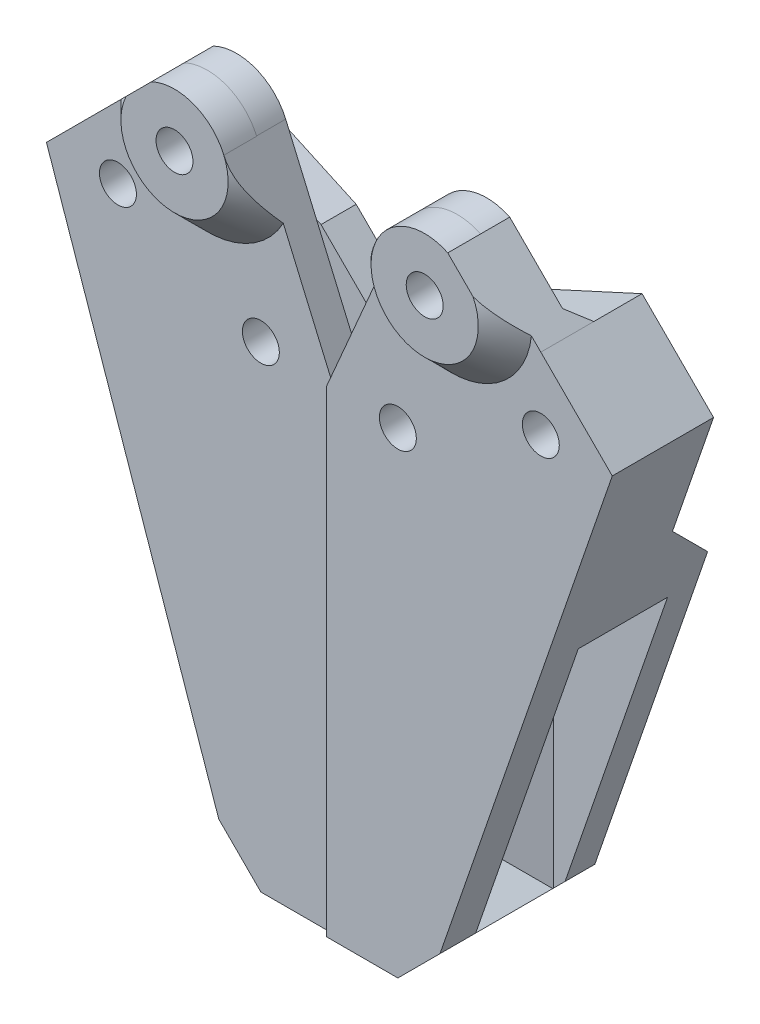
SolidWorks part; units mm, degrees
material "ABS"
ref_plane "Płaszczyzna przednia" through (0, 0, 0) normal (0, 0, 1) x (1, 0, 0)
ref_plane "Płaszczyzna górna" through (0, 0, 0) normal (0, 1, 0) x (1, 0, 0)
ref_plane "Płaszczyzna prawa" through (0, 0, 0) normal (1, 0, 0) x (0, 0, -1)
sketch "Szkic1" plane through (0, 0, 0) normal (0, 0, 1) x (1, 0, 0)
  line L0 (-24, 11) -> (-24, 23)
  line L1 (-24, 11) -> (-36, 11)
  line L2 (-24, 23) -> (-36, 11)
  line L3 (0, 0) -> (0, 12)
  line L4 (0, 12) -> (-24, 23)
  line L5 (0, 0) -> (12, 0)
  line L6 (0, 12) -> (12, 0)
  line L7 (0, 0) -> (0, -80)
  line L8 (0, -80) -> (12, -80)
  line L9 (0, -80) -> (-7.0711, -72.9289)
  line L10 (-7.0711, -72.9289) -> (-36, 11)
  line L11 (12, -80) -> (12, 0)
  circle A0 centre (0, 0) radius 3.1
  circle A1 centre (-24, 11) radius 3.1
  dimension "D1" = 6.2
  dimension "D2" = 24
  dimension "D3" = 6.2
  dimension "D4" = 11
  dimension "D5" = 12
  dimension "D6" = 12
  dimension "D7" = 12
  dimension "D8" = 12
  dimension "D9" = 80
  dimension "D10" = 12
  dimension "D11" = 135
  dimension "D12" = 10
extrude "Dodanie-wyciągnięcie1" add sketch "Szkic1" along normal blind 25 contours A1 L0 L2 L1 | A1 L1 L10 L9 L7 A0 L3 L4 L0 | A0 L5 L6 L3 | A0 L7 L8 L11 L5 region at (-28.3143, 15.3143, 0) region at (-12.4541, -19.871, 0) region at (4.3143, 4.3143, 0) region at (6.0371, -40.3066, 0)
sketch "Szkic3" plane through (12, 0, 0) normal (1, 0, 0) x (0, 0, -1)
  line L0 (-20.1, 17) -> (-20.1, -8)
  line L1 (-25, -80) -> (-25, 0) construction
  line L2 (-14.9, 17) -> (-14.9, -8)
  line L3 (-9, 17) -> (-9, -8)
  line L4 (-4, 17) -> (-4, -8)
  line L5 (0, -80) -> (0, 0) construction
  line L6 (-25, -8) -> (0, -8)
  line L7 (-25, 0) -> (0, 0) construction
  line L8 (-25, 17) -> (0, 17)
  line L9 (-25, 12) -> (-25, 0) construction
  line L10 (0, 12) -> (0, 0) construction
  line M8 (0, 0) -> (-25, 0)
  dimension "D1" = 4.9
  dimension "D2" = 10.1
  dimension "D3" = 4
  dimension "D4" = 9
  dimension "D5" = 8
  dimension "D6" = 25
extrude "Wytnij-wyciągnięcie1" cut sketch "Szkic3" against normal blind 20 contours L8 L0 L2 M8 | L0 L6 L2 M8 | L8 L3 L4 M8 | L3 L6 L4 M8 region at (12, 8.5, 17.5) region at (12, -4, 17.5) region at (12, 8.5, 6.5) region at (12, -4, 6.5)
sketch "Szkic4" plane through (12, 0, 0) normal (1, 0, 0) x (0, 0, -1)
  line L5 (-9, 12) -> (-9, 0) construction
  line L6 (-9, 4) -> (-4, 4)
  line L7 (-9, 4) -> (-9, 23)
  line L8 (-9, 23) -> (-4, 23)
  line L9 (-4, 4) -> (-4, 23)
  line L10 (-25, 23) -> (0, 23) construction
  dimension "D1" = 5
  dimension "D2" = 19
extrude "Wytnij-wyciągnięcie2" cut sketch "Szkic4" against normal blind 58
chamfer "Sfazowanie1" distance 6 angle 45 1 edges at (-8, -8, 17.5)
chamfer "Sfazowanie2" distance 12 angle 45 1 edges at (-8, 4, 6.5)
chamfer "Sfazowanie3" distance 2 angle 30 2 edges at (-8, 6.8333, 14.9) (-8, 6.8333, 20.1) first distance on face at (-8, 6.8333, 17.5)
sketch "Szkic5" plane through (0, 0, 25) normal (0, 0, 1) x (1, 0, 0)
  line L0 (-24, 23) -> (-12.8786, 34.1212)
  line L1 (-24, 23) -> (0, 12)
  line L4 (12, 0) -> (-0.7344, 29.5607)
  line L7 (12, 0) -> (0, 12)
  circle A0 centre (-9, 26) radius 2.95
  arc A5 (-0.7344, 29.5607) -> (-12.8786, 34.1212) centre (-9, 26) ccw
  line M11 (0, 12) -> (-24, 23)
  dimension "D3" = 5.9
  dimension "D1" = 26
  dimension "D2" = 9
extrude "Dodanie-wyciągnięcie2" add sketch "Szkic5" against normal blind 4.9 contours A0 M11 | A0 M11 region at (-6.0366, 21.6949, 25)
sketch "Szkic6" plane through (12, 0, 0) normal (1, 0, 0) x (0, 0, -1)
  line L1 (-9, -8) -> (0, -8)
  line L2 (-9, -8) -> (-9, 23)
  line L3 (-9, 23) -> (0, 23)
  line L4 (0, -8) -> (0, 23)
extrude "Wytnij-wyciągnięcie3" cut sketch "Szkic6" against normal blind 60
chamfer "Sfazowanie4" distance 10 angle 45 1 edges at (-8.7255, -8, 0)
sketch "Szkic8" plane through (0, 0, 25) normal (0, 0, 1) x (1, 0, 0)
  line L0 (-17.1214, 29.8785) -> (-12.8784, 34.1214)
  circle A0 centre (-9, 26) radius 3.1
  arc A1 (-17.1214, 29.8785) -> (-12.8784, 34.1214) centre (-9, 26) ccw
  dimension "D1" = 18
  dimension "D2" = 6.2
extrude "Dodanie-wyciągnięcie3" add sketch "Szkic8" along normal blind 5.5
chamfer "Sfazowanie5" distance 5.5 angle 45 1 edges at (-9.196, 17.0021, 25)
sketch "Szkic10" plane through (12, 0, 0) normal (1, 0, 0) x (0, 0, -1)
  line L0 (-20, -23) -> (-20, -75)
  line L1 (-20, -75) -> (-5, -75)
  line L2 (-5, -75) -> (-5, -23)
  line L3 (-5, -23) -> (-20, -23)
  line L4 (-25, -80) -> (0, -80) construction
  line L5 (0, -80) -> (0, -18) construction
  line L6 (-25, -80) -> (-25, 0) construction
  dimension "D1" = 5
  dimension "D2" = 5
  dimension "D3" = 5
  dimension "D4" = 5
extrude "Wytnij-wyciągnięcie6" cut sketch "Szkic10" against normal blind 70 from offset 5 offset against normal yes
chamfer "Sfazowanie9" distance 7 angle 60 4 edges at (7, -49, 20) (7, -75, 12.5) (7, -49, 5) (7, -23, 12.5) first distance on face at (7, -49, 12.5)
chamfer "Sfazowanie10" distance 3 angle 45 1 edges at (-15.4226, 19.0687, 20.1)
mirror "Lustro1" about plane through (12, 0, 25) normal (-1, 0, 0) of bodies 109
sketch "Szkic11" plane through (0, 0, 25) normal (0, 0, 1) x (1, 0, 0)
  line L0 (47.3141, 23.6858) -> (41.1214, 29.8785) construction
  line L1 (36.8784, 34.1214) -> (41.1214, 29.8785) construction
  line L2 (24.7174, 29.5212) -> (20.2365, 19.1195) construction
  line L3 (47.3141, 23.6858) -> (41.1214, 29.8785)
  line L4 (36.8784, 34.1214) -> (41.1214, 29.8785)
  line L5 (24.7174, 29.5212) -> (20.2365, 19.1195)
  line L7 (20.2365, 19.1195) -> (12, 0)
  line L8 (12, 0) -> (12, -80)
  line L9 (12, -80) -> (24, -80)
  line L10 (24, -80) -> (31.0711, -72.9289)
  line L11 (31.0711, -72.9289) -> (60, 11)
  line L12 (60, 11) -> (48, 23)
  line L13 (48, 23) -> (47.3141, 23.6858)
  line L14 (20.2365, 19.1195) -> (12, 0)
  line L15 (12, 0) -> (12, -80)
  line L16 (12, -80) -> (24, -80)
  line L17 (24, -80) -> (31.0711, -72.9289)
  line L18 (31.0711, -72.9289) -> (60, 11)
  line L19 (60, 11) -> (48, 23)
  line L20 (48, 23) -> (47.3141, 23.6858)
  arc A0 (36.8784, 34.1214) -> (24.7174, 29.5212) centre (33, 26) ccw construction
  arc A1 (20.2365, 19.1195) -> (47.3141, 23.6858) centre (33, 26) ccw
  arc A3 (36.8784, 34.1214) -> (24.7174, 29.5212) centre (33, 26) ccw
  circle A4 centre (48, 11) radius 3.1 construction
  circle A5 centre (24, 0) radius 3.1 construction
  circle A6 centre (48, 11) radius 3.1
  circle A7 centre (24, 0) radius 3.1
  circle A8 centre (33, 26) radius 2.95 construction
  circle A9 centre (33, 26) radius 2.95
  dimension "D1" = 0
extrude "Dodanie-wyciągnięcie4" add sketch "Szkic11" along normal blind 1
sketch "Szkic12" plane through (0, 0, 20.1) normal (0, 0, -1) x (-1, 0, 0)
  circle A0 centre (-33, 26) radius 2.95 construction
  circle A1 centre (-33, 26) radius 2.95
  circle A2 centre (-33, 26) radius 4.5
  dimension "D1" = 9
extrude "Dodanie-wyciągnięcie5" add sketch "Szkic12" along normal blind 0.8
chamfer "Sfazowanie11" distance 0.8 angle 45 1 edges at (33, 21.5, 20.1)
